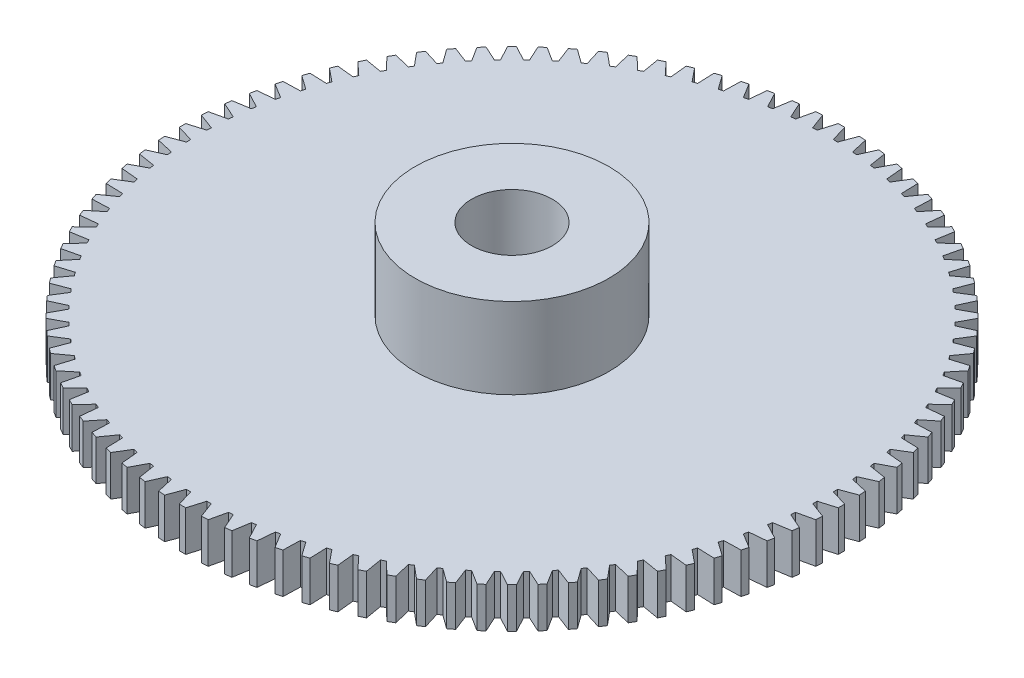
SolidWorks part; units mm, degrees
ref_plane "Front Plane" through (0, 0, 0) normal (0, 0, 1) x (1, 0, 0)
ref_plane "Top Plane" through (0, 0, 0) normal (0, 1, 0) x (1, 0, 0)
ref_plane "Right Plane" through (0, 0, 0) normal (1, 0, 0) x (0, 0, -1)
sketch "Sketch1" plane through (0, 0, 0) normal (0, 1, 0) x (1, 0, 0)
  circle A0 centre (0, 0) radius 3.175
  circle A1 centre (0, 0) radius 7.62
  dimension "D1" = 6.35
  dimension "D2" = 15.24
extrude "Boss-Extrude1" add sketch "Sketch1" along normal blind 9.525 contours A1 A0 region at (-7.4045, 0, 0)
sketch "Sketch2" plane through (0, 0, 0) normal (0, 1, 0) x (1, 0, 0)
  line L0 (0, 0) -> (0, 24.638) construction
  line L1 (-0.635, 24.6298) -> (0.635, 24.6298)
  line L2 (0, 24.638) -> (0, 25.908) construction
  line L3 (-0.254, 25.908) -> (0.254, 25.908)
  line L4 (-0.254, 25.908) -> (-0.635, 24.6298)
  line L5 (0.254, 25.908) -> (0.635, 24.6298)
  circle A0 centre (0, 0) radius 24.638
  point P11 (0, 25.908)
  dimension "D1" = 49.276
  dimension "D2" = 1.27
  dimension "D3" = 1.27
  dimension "D4" = 0.508
extrude "Boss-Extrude2" add sketch "Sketch2" along normal blind 3.175 contours L1 A0 region at (0, 0, 0.0001)
extrude "Boss-Extrude3" add sketch "Sketch2<3>" along normal blind 3.175 contours L5 L1 L4 L3
sketch "Sketch2<3>" plane through (0, 0, 0) normal (0, 1, 0) x (1, 0, 0) same geometry as "Sketch2"
pattern_circular "CirPattern1" count 96 over 360 about axis through (0, 9.525, 0) along (0, -1, 0) of "Boss-Extrude3" reverse direction yes
equation "\"Number_Teeth\" = 96"
equation "\"Diametral_Pitch\" = 48"
equation "\"Pitch_Diameter\"= \"Number_Teeth\" * \"1_inch\" / \"Diametral_Pitch\""
equation "\"Tooth_Height\"= .05in"
equation "\"Addendum\"= \"Tooth_Height\" * .4"
equation "\"Dedendum\"= \"Tooth_Height\" * .6"
equation "\"D1@Sketch2\"=\"Pitch_Diameter\"-(2*\"Dedendum\")"
equation "\"D3@Sketch2\"=\"Tooth_Height\""
equation "\"1_inch\"= 1in"
equation "\"D1@CirPattern1\"=\"Number_Teeth\""
